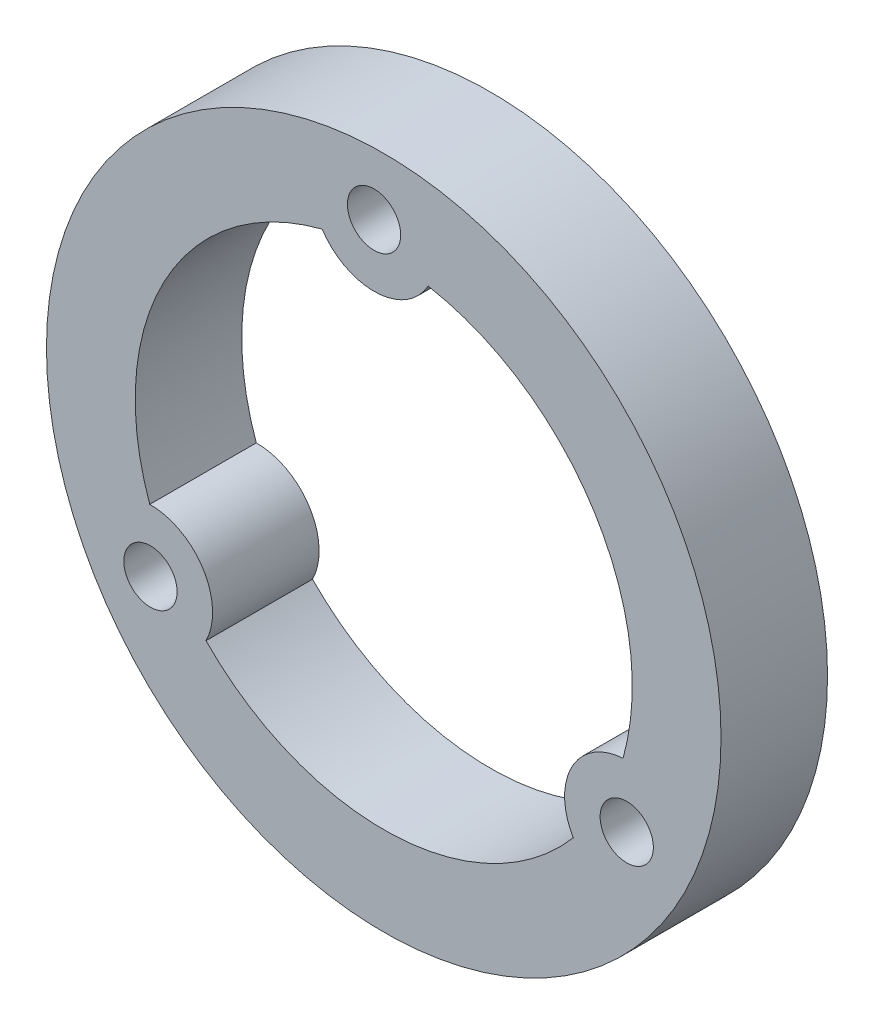
SolidWorks part; units mm, degrees
ref_plane "Plan de face" through (0, 0, 0) normal (0, 0, 1) x (1, 0, 0)
ref_plane "Plan de dessus" through (0, 0, 0) normal (0, 1, 0) x (1, 0, 0)
ref_plane "Plan de droite" through (0, 0, 0) normal (1, 0, 0) x (0, 0, -1)
sketch "Esquisse1" plane through (0, 0, 0) normal (0, 0, 1) x (1, 0, 0)
  line L0 (-0.5467, 15.4904) -> (-13.1417, -8.2186) construction
  line L1 (-13.1417, -8.2186) -> (13.6884, -7.2717) construction
  line L2 (13.6884, -7.2717) -> (-0.5467, 15.4904) construction
  circle A0 centre (0, 0) radius 19
  circle A2 centre (-0.5467, 15.4904) radius 1.5
  circle A3 centre (-13.1417, -8.2186) radius 1.5
  circle A4 centre (13.6884, -7.2717) radius 1.5
  arc A5 (-3.4686, 13.5635) -> (2.5037, 13.7743) centre (-0.5467, 15.4904) ccw
  arc A6 (-10.0121, -9.7856) -> (-13.1808, -4.7189) centre (-13.1417, -8.2186) ccw
  arc A7 (13.4806, -3.7779) -> (10.677, -9.0554) centre (13.6884, -7.2717) ccw
  arc A8 (-10.0121, -9.7856) -> (10.677, -9.0554) centre (0, 0) ccw
  arc A9 (-3.4686, 13.5635) -> (-13.1808, -4.7189) centre (0, 0) ccw
  arc A10 (13.4806, -3.7779) -> (2.5037, 13.7743) centre (0, 0) ccw
  dimension "D1" = 38
  dimension "D3" = 3
  dimension "D4" = 3
  dimension "D5" = 3
  dimension "D8" = 15.5
  dimension "D9" = 15.5
  dimension "D10" = 15.5
  dimension "D11" = 7
  dimension "D12" = 7
  dimension "D13" = 7
  dimension "D6" = 60
  dimension "D7" = 60
extrude "Boss.-Extru.2" add sketch "Esquisse1" along normal blind 6
